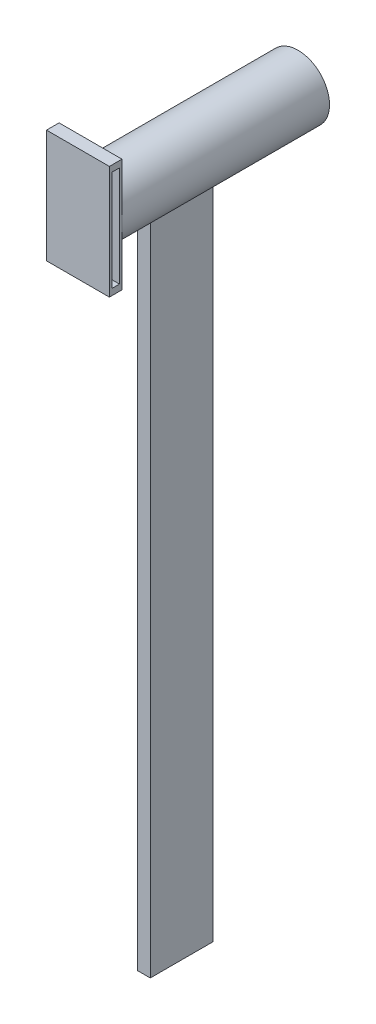
SolidWorks part; units mm, degrees
ref_plane "Front Plane" through (0, 0, 0) normal (0, 0, 1) x (1, 0, 0)
ref_plane "Top Plane" through (0, 0, 0) normal (0, 1, 0) x (1, 0, 0)
ref_plane "Right Plane" through (0, 0, 0) normal (1, 0, 0) x (0, 0, -1)
sketch "Sketch2" plane through (0, 0, 0) normal (0, 0, 1) x (1, 0, 0)
  circle A4 centre (0, 0) radius 2.5
  point P3 (25, 0)
  dimension "D1" = 5
ref_plane "Plane1" through (0, 0, 16.5) normal (0, 0, 1) x (1, 0, 0)
sketch "Sketch3" plane through (0, 0, 16.5) normal (0, 0, 1) x (1, 0, 0)
  line L0 (-2.5, 4.5) -> (2.5, 4.5)
  line L1 (-2.5, 4.5) -> (-2.5, -4.5)
  line L2 (-2.5, -4.5) -> (2.5, -4.5)
  line L3 (2.5, 4.5) -> (2.5, -4.5)
  circle A0 centre (0, 0) radius 2.5
  point P3 (0, 4.5)
  point P9 (2.5, 0)
  dimension "D1" = 5
  dimension "D2" = 9
loft "Loft1" add profiles "Sketch2", "Sketch3" connector at (0.2181, 2.4905, 0) connector at (0.0833, 2.4986, 16.5)
sketch "Sketch4" plane through (0, 0, 0) normal (0, 1, 0) x (1, 0, 0)
  line L0 (2.5, 0) -> (-2.5, 0) construction
  line L1 (-0.5, -7.25) -> (0.5, -7.25)
  line L2 (-0.5, -7.25) -> (-0.5, -12.25)
  line L3 (-0.5, -12.25) -> (0.5, -12.25)
  line L4 (0.5, -7.25) -> (0.5, -12.25)
  line L5 (-2.5, 0) -> (-2.5, -16.5) construction
  dimension "D1" = 7.25
  dimension "D2" = 2
  dimension "D3" = 5
extrude "Boss-Extrude1" add sketch "Sketch4" against normal blind 55
extrude "Boss-Extrude4" add sketch "Sketch3<7>" along normal blind 1 contours A0 L3 L0 L1 | A0 L1 L2 L3 | A0 region at (0, 3.1704, 16.5) region at (0, -3.1704, 16.5) region at (0, 0, 16.5)
sketch "Sketch3<7>" plane through (0, 0, 16.5) normal (0, 0, 1) x (1, 0, 0) same geometry as "Sketch3"
sketch "Sketch8" plane through (2.5, 0, 0) normal (1, 0, 0) x (0, 0, -1)
  line L0 (-17.5, 4.5) -> (-17.5, -4.5) construction
  line L1 (-17.3, 4) -> (-16.7, 4)
  line L2 (-17.3, 4) -> (-17.3, -4)
  line L3 (-17.3, -4) -> (-16.7, -4)
  line L4 (-16.7, 4) -> (-16.7, -4)
  line L5 (-17.5, 4.5) -> (-16.5, 4.5) construction
  point P4 (-17.3, 0)
  point P7 (-17.5, 0)
  point P8 (-17, 4)
  point P11 (-17, 4.5)
  dimension "D1" = 0.6
  dimension "D2" = 8
extrude "Cut-Extrude2" cut sketch "Sketch8" against normal through all both and the other way through all
